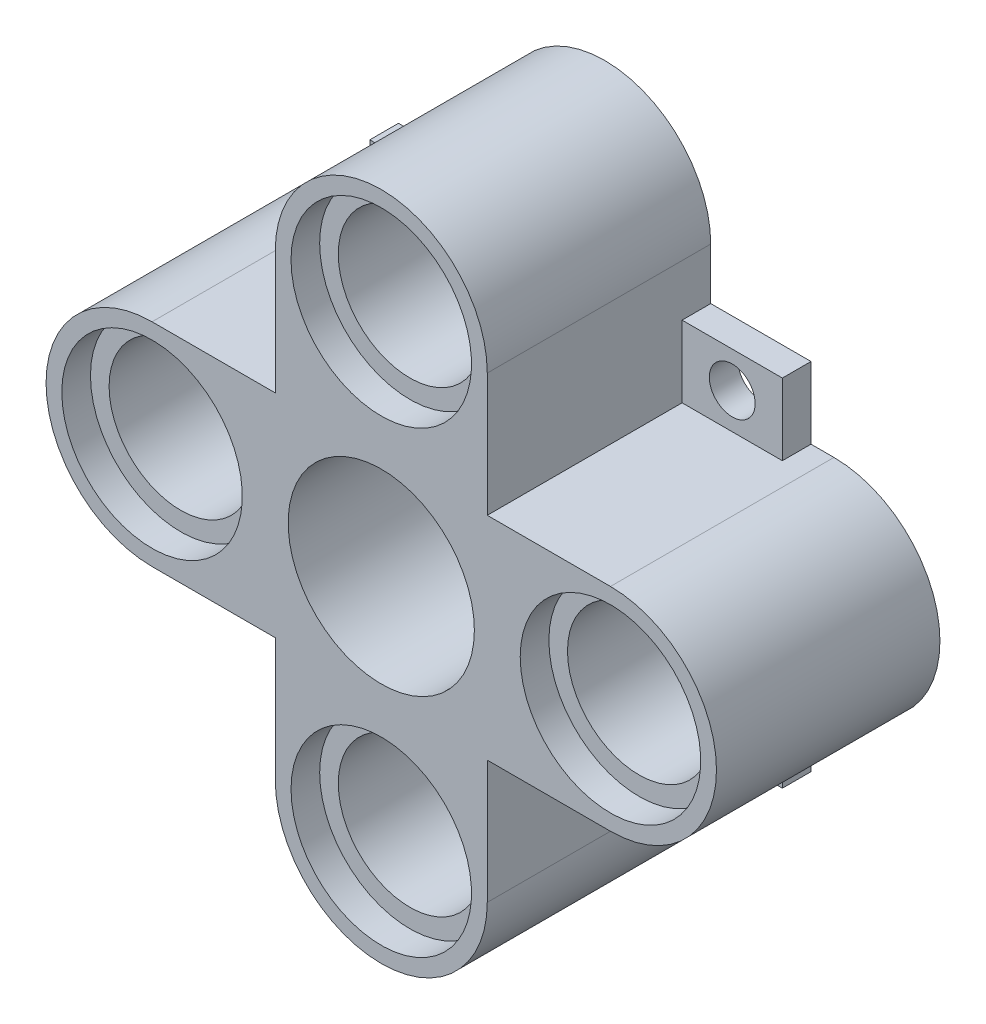
SolidWorks part; units mm, degrees
ref_plane "前视基准面" through (0, 0, 0) normal (0, 0, 1) x (1, 0, 0)
ref_plane "上视基准面" through (0, 0, 0) normal (0, 1, 0) x (1, 0, 0)
ref_plane "右视基准面" through (0, 0, 0) normal (1, 0, 0) x (0, 0, -1)
other "Configuration Table"
sketch "草图2" plane through (0, 0, 0) normal (0, 0, 1) x (1, 0, 0)
  line L0 (-8, 0) -> (8, 0) construction
  line L2 (-11.7, -3.7) -> (11.7, -3.7)
  line L3 (-11.7, -3.7) -> (-11.7, 3.7)
  line L4 (-11.7, 3.7) -> (11.7, 3.7)
  line L5 (11.7, -3.7) -> (11.7, 3.7)
  line L6 (-11.7, -3.7) -> (11.7, 3.7) construction
  line L7 (-11.7, 3.7) -> (11.7, -3.7) construction
  line L8 (-3.7, 11.7) -> (3.7, 11.7)
  line L9 (-3.7, 11.7) -> (-3.7, -11.7)
  line L10 (-3.7, -11.7) -> (3.7, -11.7)
  line L11 (3.7, 11.7) -> (3.7, -11.7)
  line L12 (-3.7, 11.7) -> (3.7, -11.7) construction
  line L13 (-3.7, -11.7) -> (3.7, 11.7) construction
  circle A0 centre (0, 0) radius 3.25
  circle A1 centre (-8, 0) radius 2.5
  circle A2 centre (8, 0) radius 2.5
  circle A3 centre (8, 0) radius 3.15
  circle A4 centre (-8, 0) radius 3.15
  circle A5 centre (-8, 0) radius 3.7
  circle A6 centre (8, 0) radius 3.7
  circle A7 centre (0, 8) radius 2.5
  circle A8 centre (0, 8) radius 3.15
  circle A9 centre (0, 8) radius 3.7
  circle A10 centre (0, -8) radius 2.5
  circle A11 centre (0, -8) radius 3.15
  circle A12 centre (0, -8) radius 3.7
  point P15 (0, 0)
  point P28 (0.9031, 8)
  point P29 (-14.0709, -7.1197)
  dimension "D2" = 5
  dimension "D3" = 6.5
  dimension "D4" = 6.3
  dimension "D1" = 8
  dimension "D5" = 7.4
extrude "凸台-拉伸1" add sketch "草图2" along normal blind 7.8 contours L4 L5 L2 L3 | L8 L11 L10 L9
sketch "草图3" plane through (0, 0, 0) normal (0, 0, -1) x (-1, 0, 0)
  line L1 (-7.2, 6.2) -> (7.2, 6.2)
  line L2 (-7.2, 6.2) -> (-7.2, -6.2)
  line L3 (-7.2, -6.2) -> (7.2, -6.2)
  line L4 (7.2, 6.2) -> (7.2, -6.2)
  line L5 (-7.2, 6.2) -> (7.2, -6.2) construction
  line L6 (-7.2, -6.2) -> (7.2, 6.2) construction
  line L7 (-7.2, 3.7) -> (7.2, 3.7)
  line L8 (-7.2, 3.7) -> (-7.2, -3.7)
  line L9 (-7.2, -3.7) -> (7.2, -3.7)
  line L10 (7.2, 3.7) -> (7.2, -3.7)
  line L11 (-7.2, 3.7) -> (7.2, -3.7) construction
  line L12 (-7.2, -3.7) -> (7.2, 3.7) construction
  point P0 (0, 0)
  point P5 (0, 0)
  point P7 (0, 0)
  dimension "D1" = 14.4
  dimension "D2" = 12.4
  dimension "D3" = 7.4
extrude "凸台-拉伸2" add sketch "草图3" against normal blind 1 contours L1 L4 L3 L2
extrude "切除-拉伸3" cut sketch "草图2<6>" along normal through all contours A9 L8 L9 | A9 L11 L8 | A6 L5 L4 | A6 L2 L5 | A12 L10 L11 | A12 L9 L10 | A5 L3 L2 | A5 L4 L3 | A7 | A1 | A0 | A2 | A10 region at (-10.8735, -2.8735, 0) region at (-10.8735, 2.8735, 0) region at (-2.8735, -10.8735, 0) region at (10.8735, -2.8735, 0) region at (2.8735, -10.8735, 0) region at (-2.8735, 10.8735, 0) region at (10.8735, 2.8735, 0) region at (2.8735, 10.8735, 0)
sketch "草图2<6>" plane through (0, 0, 0) normal (0, 0, 1) x (1, 0, 0) same geometry as "草图2"
extrude "切除-拉伸1" cut sketch "草图2<3>" along normal blind 1 contours A4 | A8 | A3 | A11
sketch "草图2<3>" plane through (0, 0, 0) normal (0, 0, 1) x (1, 0, 0) same geometry as "草图2"
extrude "切除-拉伸2" cut sketch "草图2<5>" against normal blind 1 from surface contours A4 | A11 | A3 | A8 starting at face at (-5.5, 0, 7.8)
sketch "草图2<5>" plane through (0, 0, 0) normal (0, 0, 1) x (1, 0, 0) same geometry as "草图2"
sketch "草图4" plane through (0, 0, 1) normal (0, 0, 1) x (1, 0, 0)
  line L0 (-7.2, 6.2) -> (-3.7, 3.7) construction
  line L1 (3.7, -3.7) -> (7.2, -6.2) construction
  line L3 (-7.2, 6.2) -> (-7.2, 3.7) construction
  line L4 (-3.7, 6.2) -> (-7.2, 6.2) construction
  circle A0 centre (-5.45, 4.95) radius 0.8
  circle A1 centre (5.45, 4.95) radius 0.8
  circle A2 centre (-5.45, -4.95) radius 0.8
  circle A3 centre (5.45, -4.95) radius 0.8
  point P8 (0, 0)
  point P11 (0, 0)
  point P18 (0, 0)
  point P19 (0, 0)
  dimension "D1" = 1.6
  dimension "D2" = 1.75
  dimension "D3" = 1.25
extrude "切除-拉伸4" cut sketch "草图4" against normal through all contours A0 | A1 | A3 | A2
